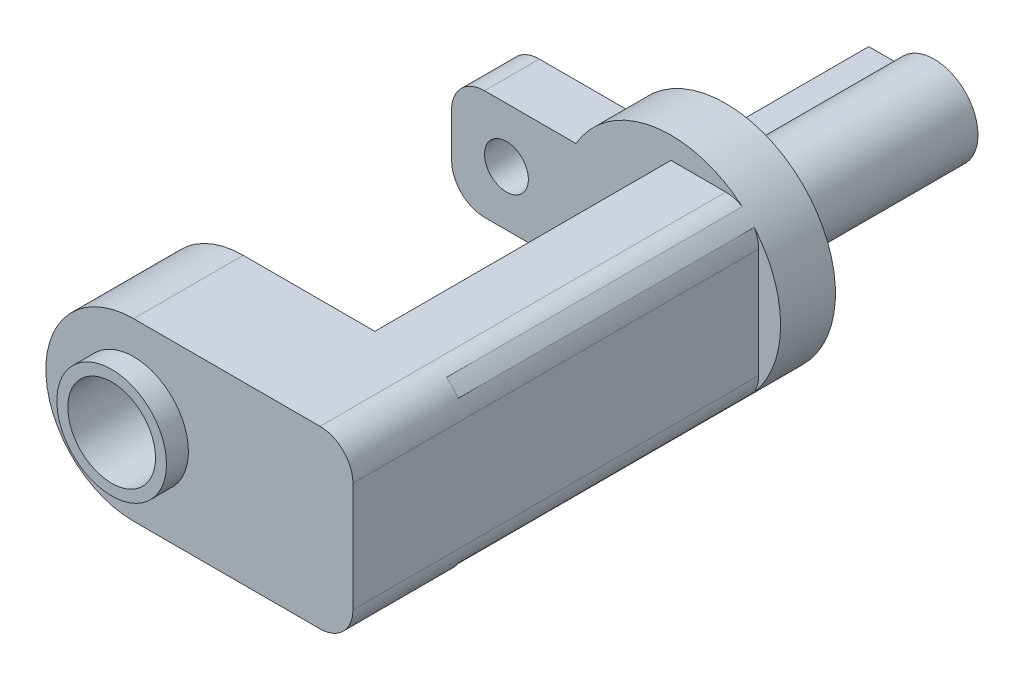
SolidWorks part; units mm, degrees
ref_plane "Plano frontal" through (0, 0, 0) normal (0, 0, 1) x (1, 0, 0)
ref_plane "Plano superior" through (0, 0, 0) normal (0, 1, 0) x (1, 0, 0)
ref_plane "Plano direito" through (0, 0, 0) normal (1, 0, 0) x (0, 0, -1)
sketch "Esboço1" plane through (0, 0, 0) normal (0, 0, 1) x (1, 0, 0)
  line L6 (-3.4641, 2) -> (-5.9641, 2)
  line L7 (-5.9641, -2) -> (-3.4641, -2)
  line L8 (-5.9641, 2) -> (-5.9641, -2)
  line L12 (-20, 5) -> (-20, -5)
  line L14 (-20, 5) -> (-8.6603, 5)
  line L15 (-20, -5) -> (-8.6603, -5)
  circle A2 centre (-15, 0) radius 2
  arc A3 (-3.4641, -2) -> (-3.4641, 2) centre (0, 0) ccw
  arc A4 (-8.6603, -5) -> (-8.6603, 5) centre (0, 0) ccw
  dimension "D1" = 4
  dimension "D2" = 4
  dimension "D3" = 10
  dimension "D4" = 3.4641
  dimension "D5" = 3.4641
  dimension "D6" = 5.9641
  dimension "D7" = 5.9641
  dimension "D8" = 8.6603
  dimension "D9" = 8.6603
  dimension "D10" = 15
  dimension "D11" = 20
  dimension "D12" = 2
  dimension "D13" = 2
  dimension "D14" = 5
  dimension "D15" = 5
  dimension "D16" = 2
  dimension "D17" = 2
extrude "Ressalto-extrusão2" add sketch "Esboço1" along normal blind 19 contours L7 A3 L6 L8 region at (-0.7108, 0, 0)
sketch "Esboço2" plane through (0, 0, 19) normal (0, 0, 1) x (1, 0, 0)
  line L9 (-20, -5) -> (-8.6603, -5)
  line L10 (-20, 5) -> (-20, -5)
  line L11 (-8.6603, 5) -> (-20, 5)
  line L12 (-20, -5) -> (-8.6603, -5)
  line L13 (-20, 5) -> (-20, -5)
  line L14 (-8.6603, 5) -> (-20, 5)
  circle A1 centre (-15, 0) radius 2
  circle A2 centre (-15, 0) radius 2
  arc A5 (-8.6603, -5) -> (-8.6603, 5) centre (0, 0) ccw
  arc A6 (-8.6603, -5) -> (-8.6603, 5) centre (0, 0) ccw
  dimension "D1" = 0
  dimension "D3" = 0
extrude "Ressalto-extrusão3" add sketch "Esboço2" along normal blind 5
fillet "Filete1" radius 3 2 edges at (-20, -5, 21.5) (-20, 5, 21.5)
sketch "Esboço3" plane through (0, 0, 24) normal (0, 0, 1) x (1, 0, 0)
  line L3 (-3.4641, 2) -> (-5.9641, 2)
  line L4 (-5.9641, 2) -> (-5.9641, -2)
  line L5 (-5.9641, -2) -> (-3.4641, -2)
  line L9 (-20, -5) -> (-8.6603, -5)
  line L10 (-20, 5) -> (-20, -5)
  line L11 (-8.6603, 5) -> (-20, 5)
  line L12 (-20, -5) -> (-8.6603, -5)
  line L13 (-20, 5) -> (-20, -5)
  line L14 (-8.6603, 5) -> (-20, 5)
  circle A0 centre (0, 0) radius 4
  circle A1 centre (-15, 0) radius 2
  circle A2 centre (-15, 0) radius 2
  arc A3 (-3.4641, -2) -> (-3.4641, 2) centre (0, 0) ccw
  arc A4 (-3.4641, -2) -> (-3.4641, 2) centre (0, 0) ccw
  arc A5 (-8.6603, -5) -> (-8.6603, 5) centre (0, 0) ccw
  arc A6 (-8.6603, -5) -> (-8.6603, 5) centre (0, 0) ccw
  dimension "D1" = 0
  dimension "D2" = 0
  dimension "D3" = 0
extrude "Ressalto-extrusão4" add sketch "Esboço3" along normal blind 17 contours A0 region at (0, 0, 24)
sketch "Esboço4" plane through (0, 0, 41) normal (0, 0, 1) x (1, 0, 0)
  line L0 (-4, -8) -> (-5, -8)
  line L1 (4, -8) -> (5, -8)
  line L2 (-4, -8) -> (4, -8)
  line L4 (-4, 8) -> (4, 8)
  line L7 (0, 0) -> (0, -22.0828) construction
  line L8 (4, 8) -> (5, 8)
  line L9 (-5, 8) -> (-4, 8)
  line L10 (5, 8) -> (4, 8)
  line L11 (-4, 8) -> (-12, 8)
  line L12 (8, -5) -> (8, 5)
  line L13 (-4, -8) -> (-12, -8)
  line L14 (4, -8) -> (5, -8)
  circle A5 centre (-12, 0) radius 4
  arc A6 (8, -5) -> (5, -8) centre (5, -5) cw
  arc A7 (8, 5) -> (5, 8) centre (5, 5) ccw
  arc A8 (-12, -8) -> (-12, 8) centre (-12, 0) cw
  circle M4 centre (0, 0) radius 4
extrude "Ressalto-extrusão6" add sketch "Esboço4" along normal blind 10 from offset 10 separate body contours L2 L1 A6 L12 A7 L8 L4 L9 L11 A8 L13 L0 A5 M4 | M4 region at (-5.1017, 0, 41) region at (0, 0, 41)
sketch "Esboço5" plane through (0, 0, 41) normal (0, 0, 1) x (1, 0, 0)
  circle A1 centre (0, 0) radius 4
  circle A2 centre (0, 0) radius 4
  dimension "D1" = 0
extrude "Ressalto-extrusão7" add sketch "Esboço5" along normal blind 10
sketch "Esboço7" plane through (0, 0, 24) normal (0, 0, 1) x (1, 0, 0)
  line L0 (0, 4) -> (0, 8)
  line L1 (0, -4) -> (0, -8)
  line L9 (-12, -8) -> (5, -8)
  line L10 (8, -5) -> (8, 5)
  line L11 (5, 8) -> (-12, 8)
  line L12 (0, -8) -> (5, -8)
  line L13 (8, -5) -> (8, 5)
  line L14 (5, 8) -> (0, 8)
  circle A0 centre (0, 0) radius 4 construction
  arc A1 (0, -4) -> (0, 4) centre (0, 0) ccw
  arc A9 (-12, 8) -> (-12, -8) centre (-12, 0) ccw
  arc A10 (5, -8) -> (8, -5) centre (5, -5) ccw
  arc A11 (8, 5) -> (5, 8) centre (5, 5) ccw
  arc A13 (5, -8) -> (6.5046, -7.5954) centre (5, -5) ccw
  arc A14 (8, 5) -> (7.5954, 6.5046) centre (5, 5) ccw
  arc A16 (7.5954, -6.5046) -> (8, -5) centre (5, -5) ccw
  arc A17 (6.5046, 7.5954) -> (5, 8) centre (5, 5) ccw
  arc A18 (8, 5) -> (5, 8) centre (5, 5) ccw construction
  arc A19 (8, 5) -> (5, 8) centre (5, 5) ccw
  arc A20 (5, -8) -> (8, -5) centre (5, -5) ccw construction
  arc A21 (5, -8) -> (8, -5) centre (5, -5) ccw
  circle M14 centre (0, 0) radius 4
  arc M18 (-8.6603, -5) -> (-8.6603, 5) centre (0, 0) ccw
  dimension "D2" = 0
extrude "Ressalto-extrusão10" add sketch "Esboço7" along normal up to surface (27 mm away) contours A17 L14 L0 L1 L12 A13 A16 L13 A14 M18 M14 region at (4.4506, 0, 24) up to face at (-0.7929, 0, 51)
fillet "Filete2" radius 10 2 edges at (0, -4, 37.5) (0, 4, 37.5)
sketch "Esboço8" plane through (0, 0, 61) normal (0, 0, 1) x (1, 0, 0)
  circle A0 centre (-12, 0) radius 4 construction
  circle A1 centre (-12, 0) radius 4
  circle A2 centre (-12, 0) radius 5
  dimension "D1" = 10
extrude "Ressalto-extrusão11" add sketch "Esboço8" along normal blind 2
